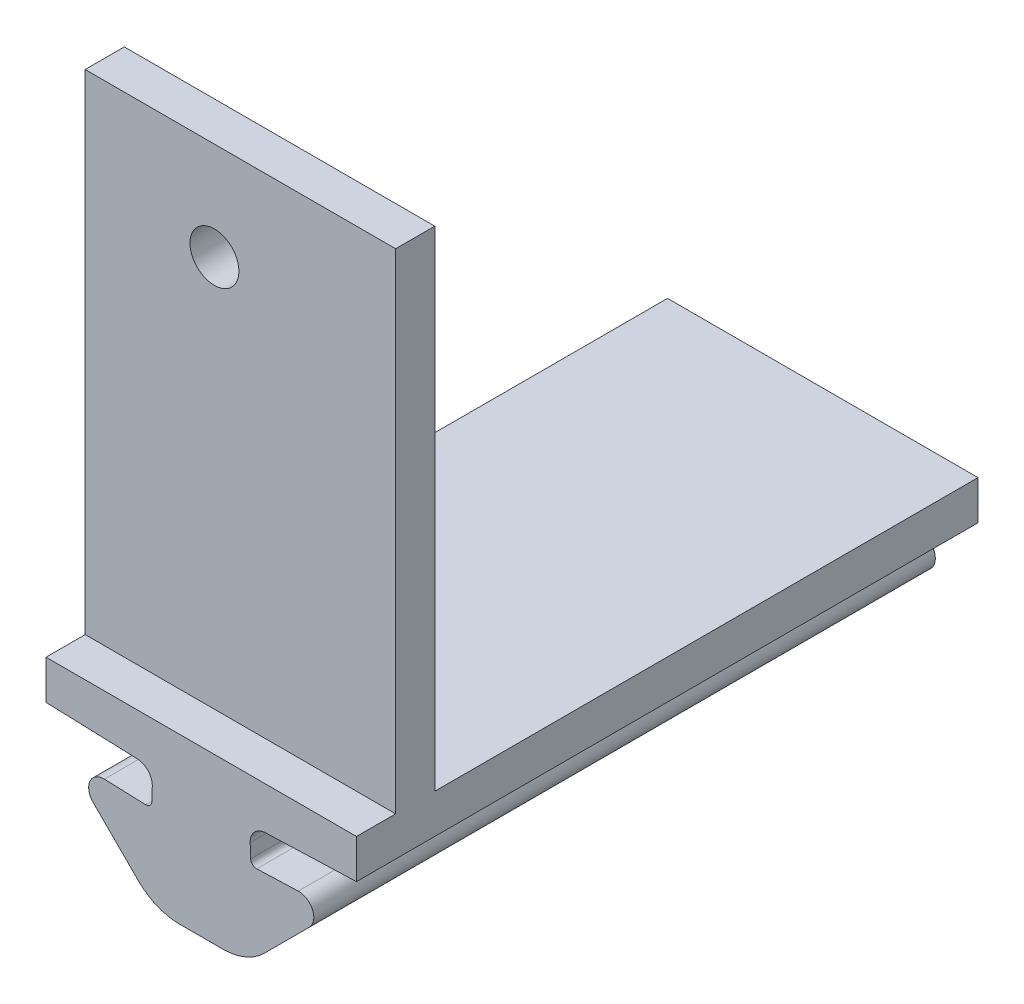
SolidWorks part; units mm, degrees
ref_plane "Front Plane" through (0, 0, 0) normal (0, 0, 1) x (1, 0, 0)
ref_plane "Top Plane" through (0, 0, 0) normal (0, 1, 0) x (1, 0, 0)
ref_plane "Right Plane" through (0, 0, 0) normal (1, 0, 0) x (0, 0, -1)
sketch "Sketch2" plane through (0, 0, 0) normal (0, 0, 1) x (1, 0, 0)
  line L1 (-50.3756, 45.6099) -> (-50.3512, 46.3094)
  line L2 (-50.6859, 45.3205) -> (-52.8037, 45.3945)
  line L6 (-55.7809, 47.2995) -> (-51.1228, 47.1369)
  line L7 (-51.0743, 41.7794) -> (-53.3751, 44.0803)
  line L8 (-47.8507, 40.9008) -> (-48.9529, 40.9008)
  line L9 (-47.8507, 40.9008) -> (-47.8507, 47.2995)
  line L10 (-47.8507, 47.2995) -> (-55.7809, 47.2995)
  arc A0 (-50.6859, 45.3205) -> (-50.3756, 45.6099) centre (-50.6754, 45.6203) ccw
  arc A7 (-50.3512, 46.3094) -> (-51.1228, 47.1369) centre (-51.1507, 46.3374) ccw
  arc A8 (-52.8037, 45.3945) -> (-53.3751, 44.0803) centre (-52.8306, 44.6248) ccw
  arc A9 (-51.0743, 41.7794) -> (-48.9529, 40.9008) centre (-48.9529, 43.9008) ccw
extrude "Boss-Extrude1" add sketch "Sketch2" along normal blind 31.75
ref_plane "Plane2" through (0, 0, 0) normal (0.7071, -0.7071, 0) x (-0.7071, -0.7071, 0)
ref_plane "Plane3" through (-42.746, 42.746, 0) normal (0.7071, -0.7071, 0) x (-0.7071, -0.7071, 0)
mirror "Mirror2" about plane through (-47.8507, 40.9008, 31.75) normal (-1, 0, 0) of "Boss-Extrude1"
ref_plane "Plane7" through (0, 47.2995, 0) normal (0, 1, 0) x (1, 0, 0)
sketch "Sketch19" plane through (0, 47.2995, 0) normal (0, 1, 0) x (1, 0, 0)
  line L0 (-55.7809, -31.75) -> (-55.7809, 0) construction
  line L1 (-55.7809, 0) -> (-39.9205, 0)
  line L2 (-55.7809, 0) -> (-55.7809, -31.75)
  line L3 (-55.7809, -31.75) -> (-39.9205, -31.75)
  line L4 (-39.9205, 0) -> (-39.9205, -31.75)
  line L5 (-39.9205, -31.75) -> (-39.9205, 0) construction
  line L6 (-39.9205, 0) -> (-55.7809, 0) construction
  dimension "D1" = 0
  dimension "D2" = 31.75
extrude "Boss-Extrude7" add sketch "Sketch19" along normal blind 2
sketch "Sketch23" plane through (0, 49.2995, 0) normal (0, 1, 0) x (1, 0, 0)
  line L0 (-55.7809, 0) -> (-55.7809, -31.75) construction
  line L1 (-55.7809, -27.75) -> (-39.9205, -27.75)
  line L2 (-55.7809, -27.75) -> (-55.7809, -29.75)
  line L3 (-55.7809, -29.75) -> (-39.9205, -29.75)
  line L4 (-39.9205, -27.75) -> (-39.9205, -29.75)
  line L5 (-39.9205, -31.75) -> (-39.9205, 0) construction
  line L6 (-39.9205, 0) -> (-55.7809, 0) construction
  dimension "D1" = 2
  dimension "D2" = 0
  dimension "D3" = 0
  dimension "D4" = 29.75
extrude "Boss-Extrude8" add sketch "Sketch23" along normal blind 25
ref_plane "Plane8" through (-39.9205, 49.2995, 27.75) normal (0, -1, 0) x (-1, 0, 0)
sketch "Sketch24" plane through (0, 0, 27.75) normal (0, 0, -1) x (-1, 0, 0)
  line L0 (39.9205, 74.2995) -> (55.7809, 74.2995) construction
  line L1 (55.7809, 74.2995) -> (55.7809, 49.2995) construction
  circle A0 centre (49.1769, 69.2995) radius 1.25
  dimension "D1" = 2.5
  dimension "D2" = 5
  dimension "D3" = 6.604
extrude "Cut-Extrude1" cut sketch "Sketch24" against normal blind 2.54
